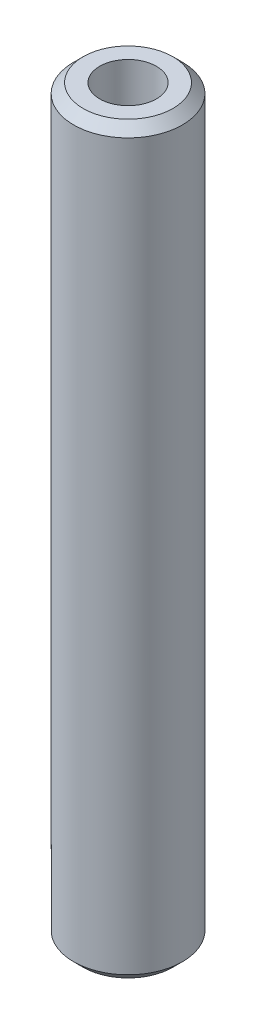
SolidWorks part; units mm, degrees
ref_plane "Front Plane" through (0, 0, 0) normal (0, 0, 1) x (1, 0, 0)
ref_plane "Top Plane" through (0, 0, 0) normal (0, 1, 0) x (1, 0, 0)
ref_plane "Right Plane" through (0, 0, 0) normal (1, 0, 0) x (0, 0, -1)
sketch "Sketch1" plane through (0, 0, 0) normal (0, 1, 0) x (1, 0, 0)
  circle A0 centre (0, 0) radius 15
  dimension "SHAFT_OD" = 30
extrude "Boss-Extrude1" add sketch "Sketch1" along normal blind 205.1308
sketch "Sketch2" plane through (0, 0, 0) normal (0, 1, 0) x (1, 0, 0)
  circle A0 centre (0, 0) radius 7.8181
  dimension "BORE_D" = 15.6363
extrude "Cut-Extrude1" cut sketch "Sketch2" along normal through all
chamfer "Chamfer1" distance 2.6209 angle 45 2 edges at (0, 205.1308, 15) (0, 0, 15)
